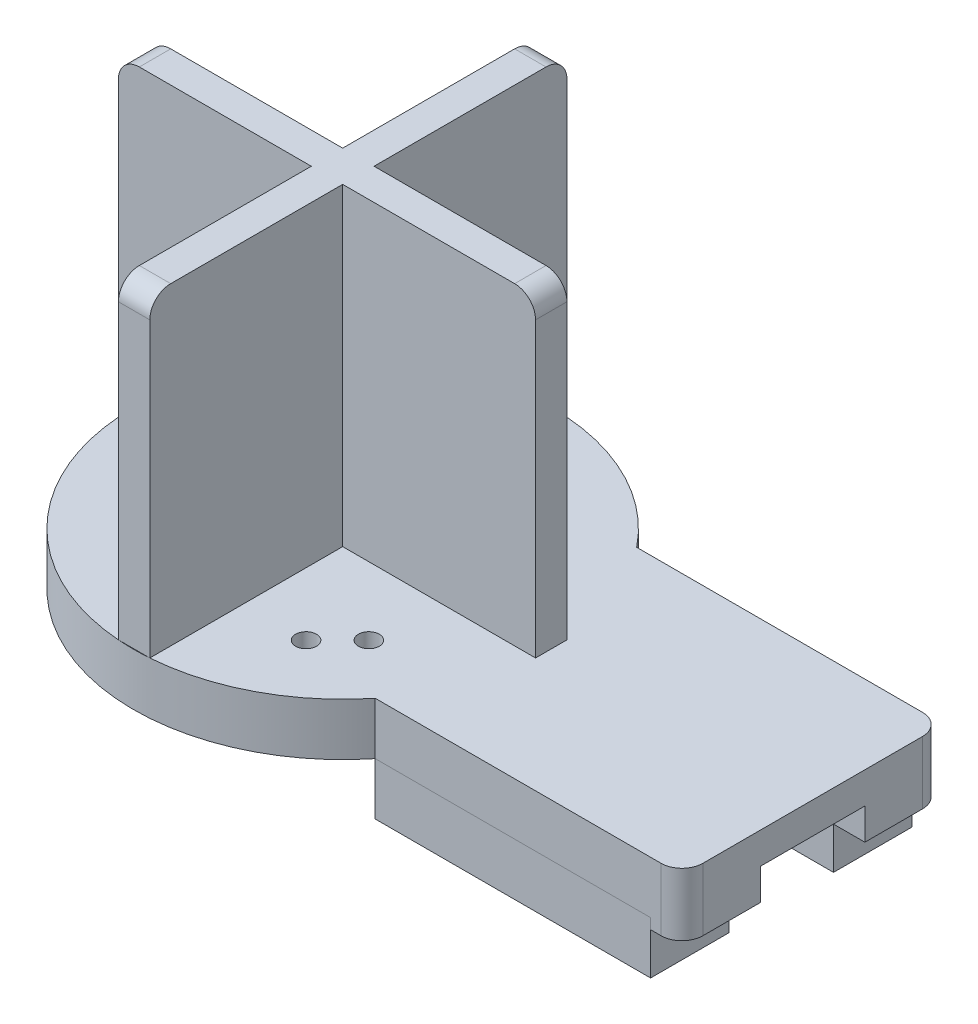
SolidWorks part; units mm, degrees
ref_plane "Front Plane" through (0, 0, 0) normal (0, 0, 1) x (1, 0, 0)
ref_plane "Top Plane" through (0, 0, 0) normal (0, 1, 0) x (1, 0, 0)
ref_plane "Right Plane" through (0, 0, 0) normal (1, 0, 0) x (0, 0, -1)
sketch "Sketch1" plane through (0, 0, 0) normal (0, 1, 0) x (1, 0, 0)
  circle A0 centre (0, 0) radius 20
  dimension "D1" = 40
extrude "Boss-Extrude1" add sketch "Sketch1" along normal blind 5
sketch "Sketch2" plane through (0, 5, 0) normal (0, 1, 0) x (1, 0, 0)
  line L1 (-1.5, -19.9437) -> (1.5, -19.9437)
  line L2 (-1.5, -19.9437) -> (-1.5, 19.9437)
  line L3 (-1.5, 19.9437) -> (1.5, 19.9437)
  line L4 (1.5, -19.9437) -> (1.5, 19.9437)
  line L5 (-1.5, -19.9437) -> (1.5, 19.9437) construction
  line L6 (-1.5, 19.9437) -> (1.5, -19.9437) construction
  line L7 (19.9437, 1.5) -> (-19.9437, 1.5)
  line L8 (19.9437, 1.5) -> (19.9437, -1.5)
  line L9 (19.9437, -1.5) -> (-19.9437, -1.5)
  line L10 (-19.9437, 1.5) -> (-19.9437, -1.5)
  line L11 (19.9437, 1.5) -> (-19.9437, -1.5) construction
  line L12 (19.9437, -1.5) -> (-19.9437, 1.5) construction
  circle A0 centre (0, 0) radius 20 construction
  point P0 (0, 0)
  point P8 (0, 0)
  dimension "D1" = 3
  dimension "D2" = 3
extrude "Boss-Extrude2" add sketch "Sketch2" along normal blind 30 contours L7 L10 L9 L2 | L9 L4 L7 L2 | L4 L9 L2 L1 | L7 L4 L3 L2 | L9 L8 L7 L4 region at (0, 5, 10.7218) region at (-10.7218, 5, 0) region at (0, 5, 0) region at (10.7218, 5, 0) region at (0, 5, -10.7218)
sketch "Sketch3" plane through (0, 5, 0) normal (0, 1, 0) x (1, 0, 0)
  line L0 (19.9437, 1.5) -> (19.9437, -1.5) construction
  line L1 (-5.0563, -12.5) -> (44.9437, -12.5)
  line L2 (-5.0563, -12.5) -> (-5.0563, 12.5)
  line L3 (-5.0563, 12.5) -> (44.9437, 12.5)
  line L4 (44.9437, -12.5) -> (44.9437, 12.5)
  line L5 (-5.0563, -12.5) -> (44.9437, 12.5) construction
  line L6 (-5.0563, 12.5) -> (44.9437, -12.5) construction
  point P0 (19.9437, 0)
  arc M3 (1.5, -19.9437) -> (19.9437, -1.5) centre (0, 0) ccw
  line M4 (19.9437, -1.5) -> (1.5, -1.5)
  dimension "D1" = 50
  dimension "D2" = 25
extrude "Boss-Extrude3" add sketch "Sketch3" against normal blind 5 contours L1 L4 L3 L2 M4 M3 region at (19.9437, 5, 0)
sketch "Sketch4" plane through (0, 0, 0) normal (0, -1, 0) x (1, 0, 0)
  line L0 (44.9437, 12.5) -> (44.9437, -12.5) construction
  line L2 (44.9437, -4.99) -> (24.9437, -4.99)
  line L3 (44.9437, -4.99) -> (44.9437, 4.99)
  line L4 (44.9437, 4.99) -> (24.9437, 4.99)
  line L5 (24.9437, -4.99) -> (24.9437, 4.99)
  line L6 (44.9437, 12.5) -> (44.9437, -12.5)
  circle A0 centre (24.9437, 0) radius 9.99
  point P13 (44.9437, 0)
  line M7 (44.9437, -12.5) -> (44.9437, 12.5)
  dimension "D1" = 19.98
  dimension "D2" = 9.98
  dimension "D3" = 20
extrude "Cut-Extrude1" cut sketch "Sketch4" against normal blind 2 contours L2 A0 L4 L5 | A0 L2 L4 M7 | L4 A0 L2 L5 region at (39.715, 0, 0) region at (22.8507, 0, 0) region at (29.7305, 0, 0)
sketch "Sketch5" plane through (0, 5, 0) normal (0, 1, 0) x (1, 0, 0)
  line L0 (44.9437, 12.5) -> (15.6125, 12.5) construction
  line L1 (1.5, 19.9437) -> (1.5, 1.5) construction
  line L2 (1.5, 1.5) -> (19.9437, 1.5) construction
  line L3 (19.9437, 1.5) -> (19.9437, -1.5) construction
  line L4 (19.9437, -1.5) -> (1.5, -1.5) construction
  line L5 (1.5, -1.5) -> (1.5, -19.9437) construction
  line L6 (15.6125, -12.5) -> (44.9437, -12.5) construction
  line L7 (44.9437, -12.5) -> (44.9437, 12.5) construction
  line L8 (-1.5, -19.9437) -> (-1.5, -1.5) construction
  line L9 (-1.5, -1.5) -> (-19.9437, -1.5) construction
  line L10 (-19.9437, 1.5) -> (-1.5, 1.5) construction
  line L11 (-1.5, 1.5) -> (-1.5, 19.9437) construction
  line L12 (44.9437, 12.5) -> (15.6125, 12.5)
  line L13 (1.5, 19.9437) -> (1.5, 1.5)
  line L14 (1.5, 1.5) -> (19.9437, 1.5)
  line L15 (19.9437, 1.5) -> (19.9437, -1.5)
  line L16 (19.9437, -1.5) -> (1.5, -1.5)
  line L17 (1.5, -1.5) -> (1.5, -19.9437)
  line L18 (15.6125, -12.5) -> (44.9437, -12.5)
  line L19 (44.9437, -12.5) -> (44.9437, 12.5)
  line L20 (-1.5, -19.9437) -> (-1.5, -1.5)
  line L21 (-1.5, -1.5) -> (-19.9437, -1.5)
  line L22 (-19.9437, 1.5) -> (-1.5, 1.5)
  line L23 (-1.5, 1.5) -> (-1.5, 19.9437)
  line L24 (0, -19.25) -> (0, 19.25) construction
  line L25 (-19.25, 0) -> (19.25, 0) construction
  arc A0 (15.6125, 12.5) -> (1.5, 19.9437) centre (0, 0) ccw construction
  arc A1 (1.5, -19.9437) -> (15.6125, -12.5) centre (0, 0) ccw construction
  arc A2 (-19.9437, -1.5) -> (-1.5, -19.9437) centre (0, 0) ccw construction
  arc A3 (-1.5, 19.9437) -> (-19.9437, 1.5) centre (0, 0) ccw construction
  arc A4 (15.6125, 12.5) -> (1.5, 19.9437) centre (0, 0) ccw
  arc A5 (1.5, -19.9437) -> (15.6125, -12.5) centre (0, 0) ccw
  arc A6 (-19.9437, -1.5) -> (-1.5, -19.9437) centre (0, 0) ccw
  arc A7 (-1.5, 19.9437) -> (-19.9437, 1.5) centre (0, 0) ccw
  circle A8 centre (-10.5, 8) radius 1
  circle A9 centre (-7.5, 11) radius 1
  circle A10 centre (10.5, 8) radius 1
  circle A11 centre (7.5, 11) radius 1
  circle A12 centre (10.5, -8) radius 1
  circle A13 centre (7.5, -11) radius 1
  circle A14 centre (-7.5, -11) radius 1
  circle A15 centre (-10.5, -8) radius 1
  dimension "D1" = 2
  dimension "D2" = 2
  dimension "D3" = 6.5
  dimension "D4" = 9
  dimension "D5" = 3
  dimension "D6" = 3
extrude "Cut-Extrude3" cut sketch "Sketch5" against normal through all contours A8 | A9 | A11 | A10 | A15 | A14 | A12 | A13 region at (-10.5, 5, -8) region at (-7.5, 5, -11) region at (10.5, 5, -8) region at (7.5, 5, -11) region at (10.5, 5, 8) region at (7.5, 5, 11) region at (-7.5, 5, 11) region at (-10.5, 5, 8)
fillet "Fillet1" radius 2 4 edges at (0, 35, -19.9437) (19.9437, 35, 0) (-19.9437, 35, 0) (0, 35, 19.9437)
sketch "Sketch6" plane through (0, 2, 0) normal (0, -1, 0) x (1, 0, 0)
  line L0 (14.9537, -13.2811) -> (14.9537, 13.2811)
  line L1 (41.9437, 12.5) -> (41.9437, -12.5)
  line L3 (33.5981, -4.99) -> (44.9437, -4.99)
  line L4 (44.9437, -4.99) -> (44.9437, 4.99)
  line L5 (44.9437, 4.99) -> (33.5981, 4.99)
  line L6 (33.5981, -4.99) -> (44.9437, -4.99)
  line L7 (44.9437, -4.99) -> (44.9437, 4.99)
  line L8 (44.9437, 4.99) -> (33.5981, 4.99)
  line L12 (33.5981, 4.99) -> (44.9437, 4.99)
  line L13 (44.9437, 4.99) -> (44.9437, 12.5)
  line L14 (44.9437, 12.5) -> (15.6125, 12.5)
  line L15 (15.6125, -12.5) -> (44.9437, -12.5)
  line L16 (44.9437, -12.5) -> (44.9437, -4.99)
  line L17 (44.9437, -4.99) -> (33.5981, -4.99)
  line L18 (33.5981, 4.99) -> (44.9437, 4.99)
  line L19 (44.9437, 4.99) -> (44.9437, 12.5)
  line L20 (44.9437, 12.5) -> (15.6125, 12.5)
  line L21 (15.6125, -12.5) -> (44.9437, -12.5)
  line L22 (44.9437, -12.5) -> (44.9437, -4.99)
  line L23 (44.9437, -4.99) -> (33.5981, -4.99)
  arc A1 (33.5981, 4.99) -> (33.5981, -4.99) centre (24.9437, 0) ccw
  arc A2 (33.5981, 4.99) -> (33.5981, -4.99) centre (24.9437, 0) ccw
  arc A4 (33.5981, 4.99) -> (33.5981, -4.99) centre (24.9437, 0) ccw
  arc A5 (15.6125, 12.5) -> (15.6125, -12.5) centre (0, 0) ccw
  arc A6 (33.5981, 4.99) -> (33.5981, -4.99) centre (24.9437, 0) ccw
  arc A7 (15.6125, 12.5) -> (15.6125, -12.5) centre (0, 0) ccw
  dimension "D2" = 0
  dimension "D3" = 3
  dimension "D1" = 0
sketch "Sketch7" plane through (0, 0, 0) normal (0, -1, 0) x (1, 0, 0)
  line L0 (41.9437, 12.5) -> (41.9437, -12.5) construction
  line L1 (14.9537, -13.2811) -> (14.9537, 13.2811) construction
  line L2 (41.9437, 12.5) -> (41.9437, -12.5)
  line L3 (14.9537, -13.2811) -> (14.9537, 13.2811)
  line L6 (33.5981, 4.99) -> (44.9437, 4.99)
  line L7 (44.9437, 4.99) -> (44.9437, 12.5)
  line L8 (44.9437, 12.5) -> (15.6125, 12.5)
  line L9 (15.6125, -12.5) -> (44.9437, -12.5)
  line L10 (44.9437, -12.5) -> (44.9437, -4.99)
  line L11 (44.9437, -4.99) -> (33.5981, -4.99)
  line L12 (33.5981, 4.99) -> (44.9437, 4.99)
  line L13 (44.9437, 4.99) -> (44.9437, 12.5)
  line L14 (44.9437, 12.5) -> (15.6125, 12.5)
  line L15 (15.6125, -12.5) -> (44.9437, -12.5)
  line L16 (44.9437, -12.5) -> (44.9437, -4.99)
  line L17 (44.9437, -4.99) -> (33.5981, -4.99)
  arc A0 (33.5981, 4.99) -> (33.5981, -4.99) centre (24.9437, 0) ccw construction
  arc A1 (33.5981, 4.99) -> (33.5981, -4.99) centre (24.9437, 0) ccw
  arc A2 (33.5981, 4.99) -> (33.5981, -4.99) centre (24.9437, 0) ccw
  arc A3 (15.6125, 12.5) -> (15.6125, -12.5) centre (0, 0) ccw
  arc A4 (33.5981, 4.99) -> (33.5981, -4.99) centre (24.9437, 0) ccw
  arc A5 (15.6125, 12.5) -> (15.6125, -12.5) centre (0, 0) ccw
  line M14 (33.5981, 4.99) -> (44.9437, 4.99)
  line M15 (44.9437, 4.99) -> (44.9437, 12.5)
  line M16 (44.9437, 12.5) -> (15.6125, 12.5)
  line M18 (15.6125, -12.5) -> (44.9437, -12.5)
  line M19 (44.9437, -12.5) -> (44.9437, -4.99)
  line M20 (44.9437, -4.99) -> (33.5981, -4.99)
  dimension "D1" = 0
extrude "Boss-Extrude4" add sketch "Sketch7" along normal blind 1 contours L2 M16 M14 M15 | L2 M20 M18 M19 region at (43.4437, 0, 8.745) region at (43.4437, 0, -8.745)
sketch "Sketch8" plane through (0, 0, 0) normal (0, -1, 0) x (1, 0, 0)
  line L0 (33.5981, -4.99) -> (44.9437, -4.99) construction
  line L1 (44.9437, 4.99) -> (33.5981, 4.99) construction
  line L2 (14.9537, -13.2811) -> (14.9537, 13.2811) construction
  line L3 (33.5981, -4.99) -> (44.9437, -4.99)
  line L4 (44.9437, 4.99) -> (33.5981, 4.99)
  line L5 (14.9537, -13.2811) -> (14.9537, 13.2811)
  line L6 (41.9437, -12.5) -> (41.9437, -4.99)
  line L7 (41.9437, -4.99) -> (33.5981, -4.99)
  line L8 (33.5981, 4.99) -> (41.9437, 4.99)
  line L9 (41.9437, 4.99) -> (41.9437, 12.5)
  line L10 (41.9437, 12.5) -> (15.6125, 12.5)
  line L11 (15.6125, -12.5) -> (41.9437, -12.5)
  line L12 (41.9437, -12.5) -> (41.9437, -4.99)
  line L13 (41.9437, -4.99) -> (33.5981, -4.99)
  line L14 (33.5981, 4.99) -> (41.9437, 4.99)
  line L15 (41.9437, 4.99) -> (41.9437, 12.5)
  line L16 (41.9437, 12.5) -> (15.6125, 12.5)
  line L17 (15.6125, -12.5) -> (41.9437, -12.5)
  arc A0 (33.5981, 4.99) -> (33.5981, -4.99) centre (24.9437, 0) ccw construction
  arc A1 (33.5981, 4.99) -> (33.5981, -4.99) centre (24.9437, 0) ccw
  arc A2 (33.5981, 4.99) -> (33.5981, -4.99) centre (24.9437, 0) ccw
  arc A3 (15.6125, 12.5) -> (15.6125, -12.5) centre (0, 0) ccw
  arc A4 (33.5981, 4.99) -> (33.5981, -4.99) centre (24.9437, 0) ccw
  arc A5 (15.6125, 12.5) -> (15.6125, -12.5) centre (0, 0) ccw
  line M17 (41.9437, -12.5) -> (41.9437, -4.99)
  line M18 (41.9437, -4.99) -> (33.5981, -4.99)
  arc M19 (33.5981, -4.99) -> (33.5981, 4.99) centre (24.9437, 0) cw
  line M20 (33.5981, 4.99) -> (41.9437, 4.99)
  line M21 (41.9437, 4.99) -> (41.9437, 12.5)
  line M22 (41.9437, 12.5) -> (15.6125, 12.5)
  arc M23 (15.6125, 12.5) -> (15.6125, -12.5) centre (0, 0) ccw
  line M24 (15.6125, -12.5) -> (41.9437, -12.5)
  dimension "D1" = 0
extrude "Boss-Extrude6" add sketch "Sketch8" along normal blind 5 separate body contours L5 M19 M20 M21 M22 M23 | L5 M23 M24 M17 M18 M19 region at (29.7246, 0, -9.4055) region at (29.7246, 0, 9.4055)
fillet "Fillet2" radius 2 1 edges at (14.9537, -2.5, 13.2811)
fillet "Fillet3" radius 2 1 edges at (14.9537, -2.5, -13.2811)
fillet "Fillet4" radius 2 2 edges at (44.9437, 2, -12.5) (44.9437, 2, 12.5)
